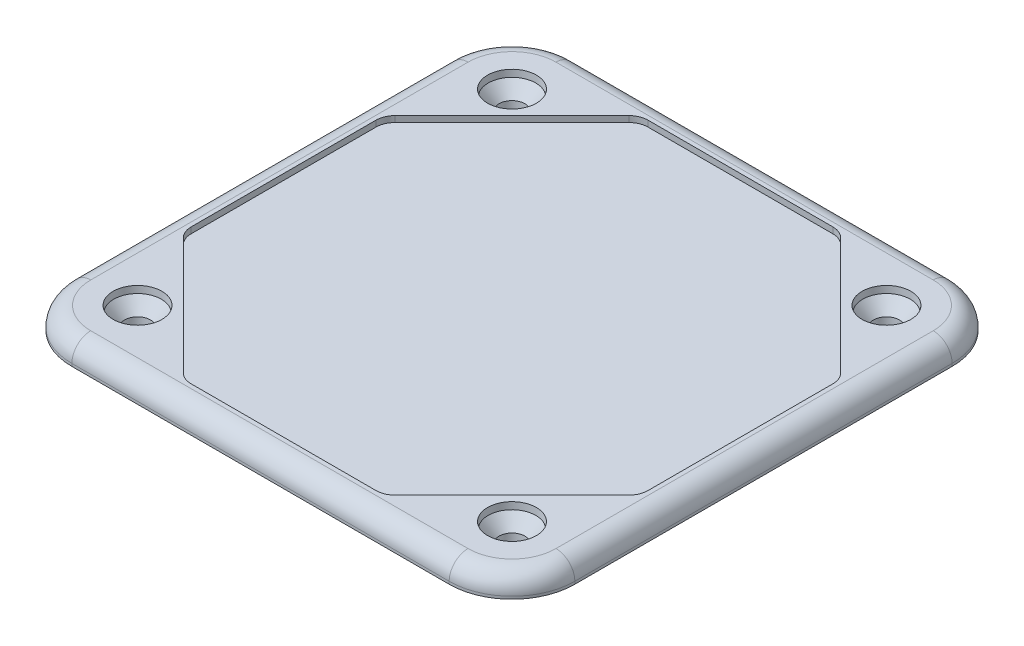
SolidWorks part; units mm, degrees
ref_plane "Front Plane" through (0, 0, 0) normal (0, 0, 1) x (1, 0, 0)
ref_plane "Top Plane" through (0, 0, 0) normal (0, 1, 0) x (1, 0, 0)
ref_plane "Right Plane" through (0, 0, 0) normal (1, 0, 0) x (0, 0, -1)
sketch "Sketch1" plane through (0, 0, 0) normal (0, 1, 0) x (1, 0, 0)
  line L0 (31.8135, 31.8135) -> (-31.8135, 31.8135)
  line L1 (-31.8135, 31.8135) -> (-31.8135, -31.8135)
  line L2 (-31.8135, -31.8135) -> (31.8135, -31.8135)
  line L3 (31.8135, -31.8135) -> (31.8135, 31.8135)
extrude "Boss-Extrude1" add sketch "Sketch1" against normal blind 2.7178
sketch "Sketch2" plane through (0, 0, 0) normal (0, 1, 0) x (-1, 0, 0)
  line L0 (12.6857, -28.8925) -> (28.8925, -12.6857)
  line L1 (28.8925, -12.6857) -> (28.8925, 12.6857)
  line L2 (28.8925, 12.6857) -> (12.6857, 28.8925)
  line L3 (12.6857, 28.8925) -> (-12.6857, 28.8925)
  line L4 (-12.6857, 28.8925) -> (-28.8925, 12.6857)
  line L5 (-28.8925, 12.6857) -> (-28.8925, -12.6857)
  line L6 (-28.8925, -12.6857) -> (-12.6857, -28.8925)
  line L7 (-12.6857, -28.8925) -> (12.6857, -28.8925)
extrude "Cut-Extrude1" cut sketch "Sketch2" against normal blind 0.762
sketch "Sketch3" plane through (0, -2.7178, 0) normal (0, -1, 0) x (1, 0, 0)
  line L0 (29.1465, -29.1465) -> (-29.1465, -29.1465)
  line L1 (-29.1465, -29.1465) -> (-29.1465, 29.1465)
  line L2 (-29.1465, 29.1465) -> (29.1465, 29.1465)
  line L3 (29.1465, 29.1465) -> (29.1465, -29.1465)
extrude "Boss-Extrude2" add sketch "Sketch3" along normal blind 1.6002
sketch "Sketch4" plane through (0, -4.318, 0) normal (0, -1, 0) x (1, 0, 0)
  line L0 (-27.5463, -27.5463) -> (27.5463, -27.5463)
  line L1 (27.5463, -27.5463) -> (27.5463, 27.5463)
  line L2 (27.5463, 27.5463) -> (-27.5463, 27.5463)
  line L3 (-27.5463, 27.5463) -> (-27.5463, -27.5463)
extrude "Cut-Extrude2" cut sketch "Sketch4" against normal blind 1.6002
ref_plane "Plane1" through (0, 0, -23.6855) normal (0, 0, -1) x (-1, 0, 0)
sketch "Sketch5" plane through (0, 0, -23.6855) normal (0, 0, -1) x (-1, 0, 0)
  line L0 (20.5105, -4.318) -> (23.6855, -4.318)
  line L1 (23.6855, -4.318) -> (23.6855, -2.7178)
  line L2 (23.6855, -2.7178) -> (20.5105, -2.7178)
  line L3 (20.5105, -2.7178) -> (20.5105, -4.318)
  line L4 (23.6855, -4.318) -> (23.6855, -2.7178) construction
revolve "Revolve1" add sketch "Sketch5" angle 360 about L4 reverse direction yes
ref_plane "Plane2" through (0, 0, 23.6855) normal (0, 0, -1) x (-1, 0, 0)
sketch "Sketch6" plane through (0, 0, 23.6855) normal (0, 0, -1) x (-1, 0, 0)
  line L0 (-26.8605, -4.318) -> (-23.6855, -4.318)
  line L1 (-23.6855, -4.318) -> (-23.6855, -2.7178)
  line L2 (-23.6855, -2.7178) -> (-26.8605, -2.7178)
  line L3 (-26.8605, -2.7178) -> (-26.8605, -4.318)
  line L4 (-23.6855, -4.318) -> (-23.6855, -2.7178) construction
revolve "Revolve2" add sketch "Sketch6" angle 360 about L4 reverse direction yes
sketch "Sketch7" plane through (0, 0, 23.6855) normal (0, 0, -1) x (-1, 0, 0)
  line L0 (20.5105, -4.318) -> (23.6855, -4.318)
  line L1 (23.6855, -4.318) -> (23.6855, -2.7178)
  line L2 (23.6855, -2.7178) -> (20.5105, -2.7178)
  line L3 (20.5105, -2.7178) -> (20.5105, -4.318)
  line L4 (23.6855, -4.318) -> (23.6855, -2.7178) construction
revolve "Revolve3" add sketch "Sketch7" angle 360 about L4 reverse direction yes
sketch "Sketch8" plane through (0, 0, -23.6855) normal (0, 0, -1) x (-1, 0, 0)
  line L0 (-26.8605, -4.318) -> (-23.6855, -4.318)
  line L1 (-23.6855, -4.318) -> (-23.6855, -2.7178)
  line L2 (-23.6855, -2.7178) -> (-26.8605, -2.7178)
  line L3 (-26.8605, -2.7178) -> (-26.8605, -4.318)
  line L4 (-23.6855, -4.318) -> (-23.6855, -2.7178) construction
revolve "Revolve4" add sketch "Sketch8" angle 360 about L4 reverse direction yes
ref_plane "Plane3" through (0, 0, -23.6855) normal (0, 0, 1) x (1, 0, 0)
sketch "Sketch9" plane through (0, 0, -23.6855) normal (0, 0, 1) x (1, 0, 0)
  line L0 (-20.5994, 0) -> (-23.6855, 0)
  line L1 (-23.6855, 0) -> (-23.6855, -4.318)
  line L2 (-23.6855, -4.318) -> (-22.2123, -4.318)
  line L3 (-22.2123, -4.318) -> (-22.0458, -2.4149)
  line L4 (-22.0458, -2.4149) -> (-20.6725, -0.835)
  line L5 (-20.6725, -0.835) -> (-20.5994, 0)
  line L6 (-23.6855, 0) -> (-23.6855, -4.318) construction
revolve "Cut-Revolve1" cut sketch "Sketch9" angle 360 about L6 reverse direction yes
ref_plane "Plane4" through (0, 0, 23.6855) normal (0, 0, 1) x (1, 0, 0)
sketch "Sketch10" plane through (0, 0, 23.6855) normal (0, 0, 1) x (1, 0, 0)
  line L0 (26.7716, 0) -> (23.6855, 0)
  line L1 (23.6855, 0) -> (23.6855, -4.318)
  line L2 (23.6855, -4.318) -> (25.1587, -4.318)
  line L3 (25.1587, -4.318) -> (25.3252, -2.4149)
  line L4 (25.3252, -2.4149) -> (26.6985, -0.835)
  line L5 (26.6985, -0.835) -> (26.7716, 0)
  line L6 (23.6855, 0) -> (23.6855, -4.318) construction
revolve "Cut-Revolve2" cut sketch "Sketch10" angle 360 about L6 reverse direction yes
sketch "Sketch11" plane through (0, 0, 23.6855) normal (0, 0, 1) x (1, 0, 0)
  line L0 (-20.5994, 0) -> (-23.6855, 0)
  line L1 (-23.6855, 0) -> (-23.6855, -4.318)
  line L2 (-23.6855, -4.318) -> (-22.2123, -4.318)
  line L3 (-22.2123, -4.318) -> (-22.0458, -2.4149)
  line L4 (-22.0458, -2.4149) -> (-20.6725, -0.835)
  line L5 (-20.6725, -0.835) -> (-20.5994, 0)
  line L6 (-23.6855, 0) -> (-23.6855, -4.318) construction
revolve "Cut-Revolve3" cut sketch "Sketch11" angle 360 about L6 reverse direction yes
sketch "Sketch12" plane through (0, 0, -23.6855) normal (0, 0, 1) x (1, 0, 0)
  line L0 (26.7716, 0) -> (23.6855, 0)
  line L1 (23.6855, 0) -> (23.6855, -4.318)
  line L2 (23.6855, -4.318) -> (25.1587, -4.318)
  line L3 (25.1587, -4.318) -> (25.3252, -2.4149)
  line L4 (25.3252, -2.4149) -> (26.6985, -0.835)
  line L5 (26.6985, -0.835) -> (26.7716, 0)
  line L6 (23.6855, 0) -> (23.6855, -4.318) construction
revolve "Cut-Revolve4" cut sketch "Sketch12" angle 360 about L6 reverse direction yes
fillet "Fillet1" radius 7.9502 4 edges at (31.8135, -1.3589, 31.8135) (-31.8135, -1.3589, -31.8135) (-31.8135, -1.3589, 31.8135) (31.8135, -1.3589, -31.8135) tangent propagation no
fillet "Fillet2" radius 2.3876 16 edges at (-12.6857, -0.381, -28.8925) (29.4849, 0, 29.4849) (31.8135, 0, 0) (0, 0, 31.8135) (29.4849, 0, -29.4849) (-29.4849, 0, 29.4849) (0, 0, -31.8135) (-31.8135, 0, 0) (-29.4849, 0, -29.4849) (12.6857, -0.381, 28.8925) (-12.6857, -0.381, 28.8925) (-28.8925, -0.381, -12.6857) (28.8925, -0.381, 12.6857) (28.8925, -0.381, -12.6857) (12.6857, -0.381, -28.8925) (-28.8925, -0.381, 12.6857) tangent propagation no
fillet "Fillet3" radius 3.683 4 edges at (-27.5463, -3.5179, 27.5463) (27.5463, -3.5179, 27.5463) (-27.5463, -3.5179, -27.5463) (27.5463, -3.5179, -27.5463) tangent propagation no
fillet "Fillet4" radius 5.2832 4 edges at (29.1465, -3.5179, 29.1465) (29.1465, -3.5179, -29.1465) (-29.1465, -3.5179, -29.1465) (-29.1465, -3.5179, 29.1465) tangent propagation no
